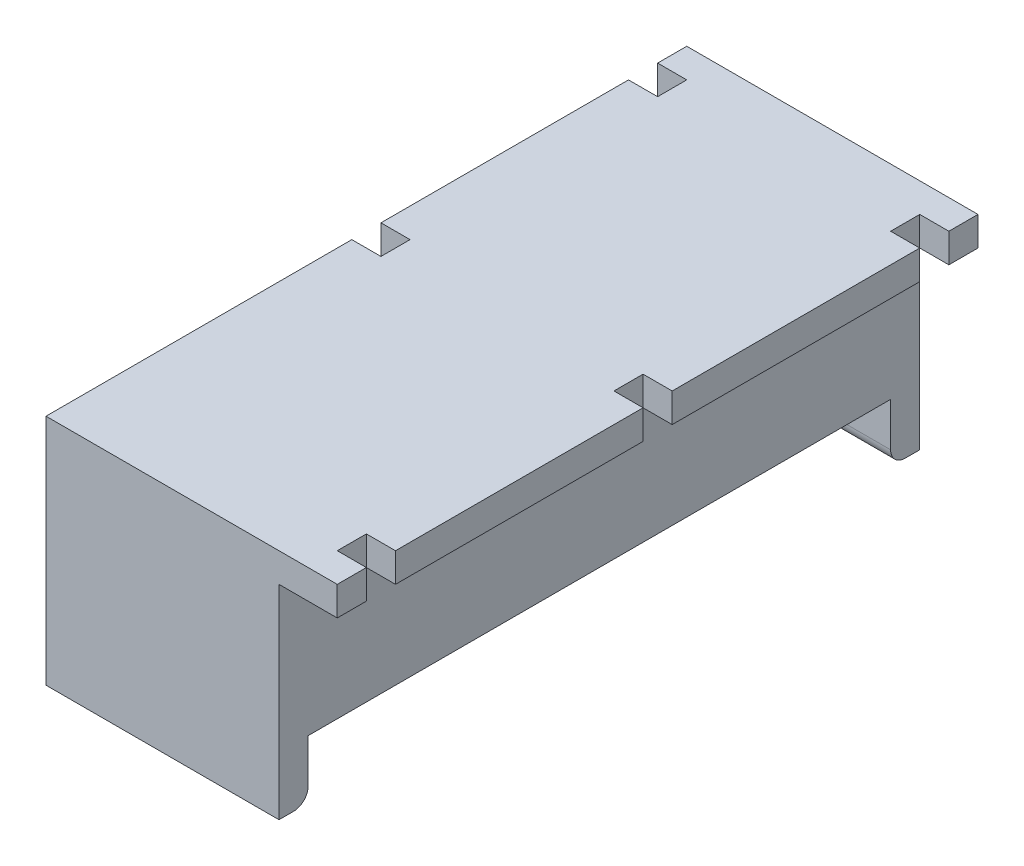
SolidWorks part; units mm, degrees
ref_plane "Front Plane" through (0, 0, 0) normal (0, 0, 1) x (1, 0, 0)
ref_plane "Top Plane" through (0, 0, 0) normal (0, 1, 0) x (1, 0, 0)
ref_plane "Right Plane" through (0, 0, 0) normal (1, 0, 0) x (0, 0, -1)
sketch "Sketch2" plane through (0, 0, 0) normal (0, 1, 0) x (1, 0, 0)
  line L0 (-22.5, -50) -> (27.5, -50)
  line L1 (-22.5, 60) -> (27.5, 60)
  line L2 (-22.5, 60) -> (-22.5, -50)
  line L4 (27.5, 60) -> (27.5, -50)
  line L5 (27.5, -50) -> (22.5, -50)
  line L6 (22.5, -50) -> (22.5, 60)
  line L7 (-17.5, -50) -> (-17.5, 60)
  line L8 (27.5, 60) -> (27.5, 55)
  line L9 (27.5, 55) -> (-17.5, 55)
  line L10 (27.5, -50) -> (27.5, -45)
  line L11 (27.5, -45) -> (-17.5, -45)
  point P0 (0, 0)
  dimension "D1" = 110
  dimension "D2" = 50
  dimension "D3" = 5
extrude "Boss-Extrude1" add sketch "Sketch2" against normal blind 30 contours L0 L7 L1 L2 | L9 L6 L1 L7 | L9 L4 L1 L6 | L11 L4 L9 L6 | L4 L11 L6 L0 | L6 L11 L7 L0 region at (-20, 0, -5) region at (2.5, 0, 47.5) region at (25, 0, 47.5) region at (2.5, 0, -57.5) region at (25, 0, -5) region at (25, 0, -57.5)
sketch "Sketch3" plane through (-22.5, 0, 0) normal (-1, 0, 0) x (0, 0, 1)
  line L0 (-60, -30) -> (-40, -30)
  line L1 (-60, -30) -> (50, -30)
  line L2 (-40, -30) -> (-30, -30)
  line L3 (-60, -30) -> (50, -30) construction
  line L4 (-30, -30) -> (-30, -20)
  line L5 (-30, -20) -> (-40, -20)
  line L6 (-40, -20) -> (-40, -30)
  line L7 (-35, -30) -> (-35, -25)
  line L8 (-35, -25) -> (-40, -25)
  line L9 (-5, -30) -> (-5, -17.8111)
  line L10 (-38, -22) -> (-32, -22)
  line L11 (-38, -22) -> (-38, -28)
  line L12 (-38, -28) -> (-32, -28)
  line L13 (-32, -22) -> (-32, -28)
  line L14 (-38, -22) -> (-32, -28) construction
  line L15 (-38, -28) -> (-32, -22) construction
  line L20 (-5, -30) -> (41.417, -30)
  line L21 (41.417, -30) -> (16.417, -30)
  line L22 (20, -15) -> (20, -25)
  line L23 (16.417, -30) -> (19.417, -30)
  line L24 (19.417, -30) -> (22.417, -30)
  line L29 (50, 0) -> (-60, 0)
  line L34 (20, -22) -> (23, -22)
  line L36 (-5, 0) -> (-5, -13.2655)
  line L37 (-5, -30) -> (45, -30)
  line L38 (45, -30) -> (45, 0)
  line L39 (45, -15) -> (20, -15)
  line L40 (17, -22) -> (23, -22)
  line L41 (17, -22) -> (17, -28)
  line L42 (17, -28) -> (23, -28)
  line L43 (23, -22) -> (23, -28)
  line L44 (17, -22) -> (23, -28) construction
  line L45 (17, -28) -> (23, -22) construction
  dimension "D1" = 20
  dimension "D2" = 6
  dimension "D3" = 6
extrude "Boss-Extrude2" add sketch "Sketch2<4>" against normal blind 5 contours L11 L6 L9 L7 region at (2.5, 0, -5)
sketch "Sketch2<4>" plane through (0, 0, 0) normal (0, 1, 0) x (1, 0, 0) same geometry as "Sketch2"
sketch "Sketch4" plane through (0, 0, 0) normal (0, 1, 0) x (1, 0, 0)
  line L0 (-22.5, 60) -> (27.5, 60)
  line L1 (27.5, 60) -> (27.5, -50)
  line L2 (27.5, -50) -> (-22.5, -50)
  line L3 (-22.5, -50) -> (-22.5, 60)
sketch "Sketch5" plane through (0, -30, 0) normal (0, -1, 0) x (1, 0, 0)
  line L0 (-22.5, 50) -> (-22.5, 45)
  line L1 (-22.5, 50) -> (-22.5, -60) construction
  line L2 (-22.5, 45) -> (17.5, 45)
  line L3 (22.5, 45) -> (-17.5, 45) construction
  line L4 (17.5, 45) -> (17.5, -55)
  line L5 (22.5, -55) -> (-17.5, -55) construction
  line L6 (17.5, -55) -> (-22.5, -55)
  line L7 (-22.5, 45) -> (-22.5, 40)
  line L8 (-22.5, 40) -> (12.5, 40)
  line L9 (12.5, 40) -> (12.5, -50)
  line L10 (12.5, -50) -> (-22.5, -50)
  line L11 (-17.5, -55) -> (-17.5, -50)
  line L12 (-17.5, 45) -> (-17.5, -55) construction
  line L13 (-22.5, 50) -> (27.5, 50)
  line L14 (27.5, 50) -> (27.5, -60)
  line L15 (27.5, -60) -> (-22.5, -60)
  line L16 (-22.5, -60) -> (-22.5, -55)
  line L17 (-17.5, 45) -> (-17.5, 40)
  line L18 (-22.5, 45) -> (-22.5, 40)
  line L19 (-22.5, -50) -> (-22.5, -55)
  line M1 (22.5, -55) -> (-17.5, -55)
  line M2 (-17.5, -55) -> (-17.5, 45)
  line M3 (-17.5, 45) -> (22.5, 45)
  line M4 (22.5, 45) -> (22.5, -55)
  line M5 (27.5, 50) -> (-22.5, 50)
  line M6 (-22.5, 50) -> (-22.5, -60)
  line M7 (-22.5, -60) -> (27.5, -60)
  line M8 (27.5, -60) -> (27.5, 50)
extrude "Cut-Extrude2" cut sketch "Sketch5" against normal blind 25 contours L6 L2 M1 M6 M7 M8 M5 M3 M4 region at (2.5, -30, 48.7917)
extrude "Boss-Extrude3" add sketch "Sketch5<3>" against normal blind 25 contours L9 L10 L4 L8 M2 M1 M3 region at (0, -30, 43.9405)
sketch "Sketch5<3>" plane through (0, -30, 0) normal (0, -1, 0) x (1, 0, 0) same geometry as "Sketch5"
sketch "Sketch10" plane through (0, -5, 0) normal (0, -1, 0) x (1, 0, 0)
  line L0 (-22.5, 50) -> (17.5, 50)
  line L3 (17.5, 45) -> (-22.5, 45)
  line L4 (-22.5, 45) -> (-22.5, 50)
  line L7 (17.5, -60) -> (-22.5, -60)
  line L8 (-22.5, -60) -> (-22.5, -55)
  line L9 (-22.5, -55) -> (17.5, -55)
  line L10 (17.5, 45) -> (17.5, 50)
  line L11 (17.5, -55) -> (17.5, -60)
extrude "Boss-Extrude4" add sketch "Sketch10" along normal blind 35
sketch "Sketch11" plane through (0, 0, 0) normal (0, 1, 0) x (1, 0, 0)
  line L0 (-22.5, 60) -> (27.5, 60)
  line L1 (27.5, 60) -> (27.5, -50)
  line L2 (27.5, -50) -> (-22.5, -50)
  line L3 (-22.5, -50) -> (-22.5, 60)
  line L4 (27.5, 60) -> (27.5, 55)
  line L5 (27.5, 55) -> (-22.5, 55)
  line L6 (27.5, 60) -> (22.5, 60)
  line L7 (22.5, 60) -> (22.5, -50)
  line L8 (27.5, -50) -> (27.5, -45)
  line L9 (27.5, -45) -> (-22.5, -45)
  line L10 (27.5, -45) -> (27.5, -40)
  line L11 (22.5, -40) -> (27.5, -40)
  line L12 (27.5, -45) -> (22.5, -45)
  line L13 (22.5, -40) -> (22.5, -45)
  line L14 (27.5, -40) -> (27.5, -45)
  line L19 (22.5, -40) -> (24, -40)
  line L20 (22.5, -40) -> (22.5, -41.5)
  line L21 (27.5, -40) -> (27.5, -45)
  line L22 (27.5, -45) -> (22.5, -45)
  line L23 (22.5, -45) -> (22.5, -40)
  line L24 (27.5, -45) -> (22.5, -45)
  line L29 (-22.5, -45) -> (-17.5, -45)
  line L30 (-17.5, -40) -> (-17.5, -45)
  line L31 (22.5, -40) -> (23.5, -40)
  line L32 (22.5, -40) -> (22.5, -41)
  line L33 (22.5, -45) -> (22.5, 5)
  line L38 (27.5, -40) -> (22.5, -40)
  line L39 (27.5, -40) -> (27.5, -45)
  line L40 (22.5, -20) -> (24, -20)
  line L45 (27.5, 55) -> (27.5, -45)
  line L46 (27.5, 5) -> (27.5, 7.5)
  line L47 (27.5, 5) -> (27.5, 2.5)
  line L48 (27.5, 2.5) -> (22.5, 2.5)
  line L49 (22.5, 2.5) -> (22.5, 7.5)
  line L50 (22.5, 7.5) -> (27.5, 7.5)
  line L51 (27.5, 55) -> (27.5, 50)
  line L52 (27.5, 50) -> (22.5, 50)
  line L53 (22.5, 50) -> (22.5, 55)
  line L54 (22.5, 55) -> (27.5, 55)
  line L55 (27.5, 55) -> (-22.5, 55)
  line L56 (2.5, 55) -> (2.5, 50)
  line L57 (22.5, -40) -> (27.5, -40)
  line L58 (27.5, -45) -> (27.5, -40)
  line L59 (27.5, -45) -> (22.5, -45)
  line L60 (22.5, -40) -> (22.5, -45)
  line L61 (27.5, -45) -> (22.5, -45)
  line L62 (22.5, -40) -> (22.5, -45)
  line L63 (27.5, -40) -> (22.5, -45) construction
  line L64 (27.5, -45) -> (22.5, -40) construction
  line L65 (-22.5, -40) -> (-17.5, -40)
  line L66 (-22.5, -40) -> (-22.5, -45)
  line L67 (-17.5, 2.5) -> (-17.5, 7.5)
  line L68 (-22.5, 2.5) -> (-17.5, 2.5)
  line L69 (-22.5, 5) -> (-22.5, 2.5)
  line L70 (-22.5, 5) -> (-22.5, 7.5)
  line L71 (-17.5, 7.5) -> (-22.5, 7.5)
  line L72 (-17.5, 55) -> (-22.5, 55)
  line L73 (-17.5, 50) -> (-17.5, 55)
  line L74 (-22.5, 50) -> (-17.5, 50)
  line L75 (-22.5, 55) -> (-22.5, 50)
  line M24 (-22.5, 60) -> (-22.5, -50)
extrude "Cut-Extrude5" cut sketch "Sketch11" against normal blind 6 contours L52 L45 L5 L7 | L50 L7 L48 L45 | L11 L7 L23 L13 L9 L1 L19 region at (25, 0, -52.5) region at (25, 0, -5) region at (25, 0, 42.5)
extrude "Cut-Extrude6" cut sketch "Sketch11<4>" against normal blind 4.99 contours L67 L71 L68 M24 | L75 L74 L73 L72 region at (-20, 0, -5)
sketch "Sketch11<4>" plane through (0, 0, 0) normal (0, 1, 0) x (1, 0, 0) same geometry as "Sketch11"
fillet "Fillet1" radius 2.5 2 edges at (-2.5, -40, -55) (-2.5, -40, 45)
sketch "Sketch12" plane through (-22.5, 0, 0) normal (-1, 0, 0) x (0, 0, 1)
  line L0 (-55, -30) -> (45, -30)
  line L1 (45, -30) -> (25.0609, -30)
  line L2 (25.0609, -30) -> (20.0609, -30)
extrude "Cut-Extrude8" cut sketch "Sketch3" against normal blind 5 contours L43 L34 L40 L41 L42 region at (-22.5, -22.0849, 21.5)
